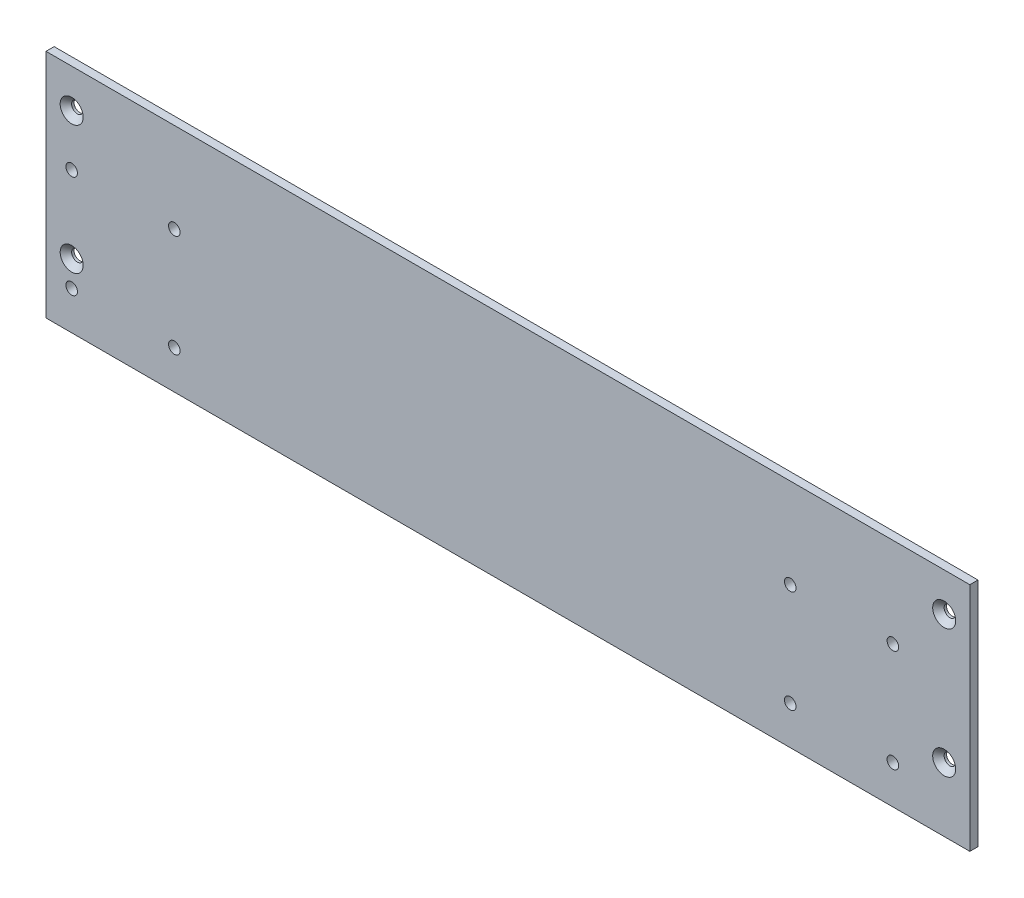
SolidWorks part; units mm, degrees
ref_plane "Front Plane" through (0, 0, 0) normal (0, 0, 1) x (1, 0, 0)
ref_plane "Top Plane" through (0, 0, 0) normal (0, 1, 0) x (1, 0, 0)
ref_plane "Right Plane" through (0, 0, 0) normal (1, 0, 0) x (0, 0, -1)
sketch "Sketch1" plane through (0, 0, 0) normal (0, 0, 1) x (1, 0, 0)
  line L1 (-180, -45) -> (180, -45)
  line L2 (-180, -45) -> (-180, 45)
  line L3 (-180, 45) -> (180, 45)
  line L4 (180, -45) -> (180, 45)
  line L5 (-180, -45) -> (180, 45) construction
  line L6 (-180, 45) -> (180, -45) construction
  point P0 (0, 0)
  dimension "D1" = 360
  dimension "D2" = 90
extrude "Boss-Extrude1" add sketch "Sketch1" along normal blind 3.175
hole_wizard "M4 Clearance Hole1" positions "Sketch2" profile "Sketch4" hole size "M4" standard "ANSI Metric" end condition through all
sketch "Sketch2" plane through (0, 0, 3.175) normal (0, 0, 1) x (1, 0, 0)
  line L1 (-170, -30) -> (-130, -30)
  line L2 (-170, -30) -> (-170, 10)
  line L3 (-170, 10) -> (-130, 10)
  line L4 (-130, -30) -> (-130, 10)
  line L5 (-170, -30) -> (-130, 10) construction
  line L6 (-170, 10) -> (-130, -30) construction
  line L7 (-180, 45) -> (-180, -45) construction
  line L8 (110, -30) -> (150, -30)
  line L9 (110, -30) -> (110, 10)
  line L10 (110, 10) -> (150, 10)
  line L11 (150, -30) -> (150, 10)
  line L12 (110, -30) -> (150, 10) construction
  line L13 (110, 10) -> (150, -30) construction
  line L14 (-180, -45) -> (180, -45) construction
  line L15 (180, -45) -> (180, 45) construction
  point P1 (-130, 10)
  point P48 (-170, -30)
  point P49 (-170, 10)
  point P50 (-130, -30)
  point P53 (-150, -10)
  point P66 (110, 10)
  point P69 (150, 10)
  point P72 (150, -30)
  point P75 (110, -30)
  point P81 (130, -10)
  dimension "D1" = 40
  dimension "D2" = 40
  dimension "D3" = 30
  dimension "D5" = 35
  dimension "D6" = 50
  dimension "D4" = 2
sketch "Sketch4" plane through (-130, 10, 3.175) normal (1, 0, 0) x (0, -1, 0)
  line L0 (0, 0) -> (0, 3.175)
  line L1 (0, 3.175) -> (2.25, 3.175)
  line L2 (2.25, 3.175) -> (2.25, 0)
  line L5 (2.25, 0) -> (0, 0)
  line L11 (0, -6.35) -> (0, 107.95) construction
  dimension "Thru Hole Dia." = 4.5
  dimension "Thru Hole Depth" = 3.175
hole_wizard "CSK for M4 SFHCS1" positions "Sketch5" profile "Sketch7" countersink size "M4" standard "ANSI Metric"
sketch "Sketch5" plane through (0, 0, 3.175) normal (0, 0, 1) x (1, 0, 0)
  line L1 (-170, -20) -> (170, -20)
  line L2 (-170, -20) -> (-170, 30)
  line L3 (-170, 30) -> (170, 30)
  line L4 (170, -20) -> (170, 30)
  line L5 (-170, -20) -> (170, 30) construction
  line L6 (-170, 30) -> (170, -20) construction
  line L7 (-180, 45) -> (-180, -45) construction
  line L8 (180, -45) -> (180, 45) construction
  line L9 (-180, -45) -> (180, -45) construction
  point P2 (170, 30)
  point P67 (-170, -20)
  point P68 (-170, 30)
  point P69 (170, -20)
  dimension "D1" = 50
  dimension "D2" = 10
  dimension "D3" = 10
  dimension "D4" = 25
sketch "Sketch7" plane through (170, 30, 3.175) normal (1, 0, 0) x (0, -1, 0)
  line L0 (0, 0) -> (0, 11.4519)
  line L1 (0, 11.4519) -> (2.25, 10.1)
  line L2 (2.25, 10.1) -> (2.25, 2.23)
  line L3 (2.25, 2.23) -> (4.48, 0)
  line L5 (4.48, 0) -> (0, 0)
  line L6 (-2.25, 2.23) -> (-4.48, 0) construction
  line L10 (0, 11.4519) -> (-2.25, 10.1) construction
  line L11 (0, -6.35) -> (0, 107.95) construction
  dimension "Hole Dia." = 4.5
  dimension "Hole Depth" = 10.1
  dimension "Near C'Sink Dia." = 8.96
  dimension "Near C'Sink Angle" = 90
  dimension "Drill Angle" = 118
